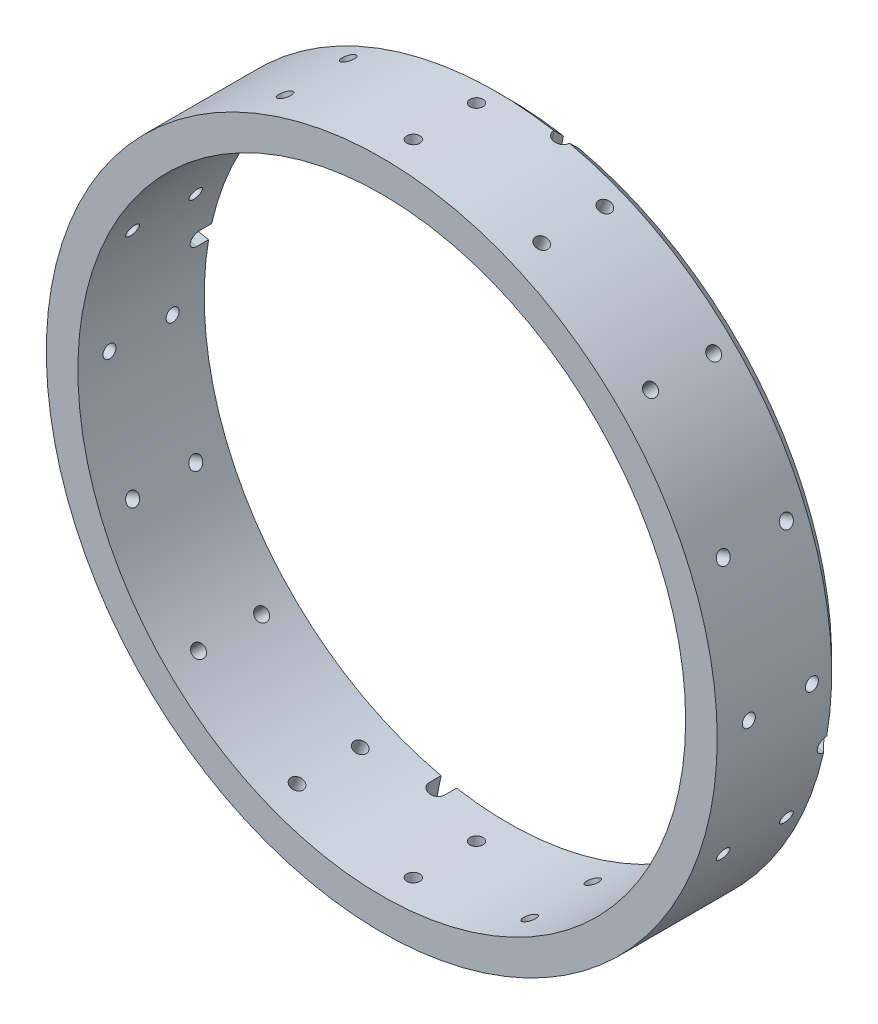
SolidWorks part; units mm, degrees
material "6063-T6"
ref_plane "Płaszczyzna przednia" through (0, 0, 0) normal (0, 0, 1) x (1, 0, 0)
ref_plane "Płaszczyzna górna" through (0, 0, 0) normal (0, 1, 0) x (1, 0, 0)
ref_plane "Płaszczyzna prawa" through (0, 0, 0) normal (1, 0, 0) x (0, 0, -1)
sketch "Szkic1" plane through (0, 0, 0) normal (0, 0, 1) x (1, 0, 0)
  circle A0 centre (0, 0) radius 85
  circle A1 centre (0, 0) radius 77
  dimension "D1" = 170
  dimension "D2" = 8
extrude "Dodanie-wyciągnięcie1" add sketch "Szkic1" along normal blind 32
sketch "Szkic2" plane through (0, 0, 32) normal (0, 0, 1) x (1, 0, 0)
  line L0 (0, 46.3429) -> (0, 98.4468) construction
  circle A0 centre (0, 0) radius 85 construction
  circle A1 centre (0, 0) radius 85
  point P6 (0, 85)
sketch3d "Szkic 3D1"
sketch "Szkic3" plane through (0, 85, 0) normal (0, 1, 0) x (1, 0, 0)
  line L0 (0, 18.1334) -> (0, -45.2976) construction
  line L1 (77, 0) -> (-77, 0) construction
  circle A0 centre (0, -8) radius 1.65
  circle A1 centre (0, -24) radius 1.65
  dimension "D1" = 3.3
  dimension "D2" = 3.3
  dimension "D3" = 8
  dimension "D4" = 16
extrude "Wytnij-wyciągnięcie1" cut sketch "Szkic3" against normal blind 32
pattern_circular "Szyk kołowy1" count 16 over 360 about axis through (0, 0, 32) along (0, 0, -1) of "Wytnij-wyciągnięcie1" reverse direction yes
chamfer "Sfazowanie1" distance 3 angle 45 1 edges at (85, 0, 0)
sketch "Szkic5" plane through (0, 0, 0) normal (0, 0, -1) x (-1, 0, 0)
  line L0 (0, 109.5264) -> (0, 0) construction
  line L1 (-23.4011, 117.6453) -> (0, 0) construction
  line L2 (-18.5397, 82.9535) -> (-16.9785, 75.1048)
  line L3 (-14.6165, 83.7338) -> (-13.0553, 75.8852)
  line L5 (-21.4395, 118.0355) -> (1.9616, 0.3902) construction
  line L6 (-25.3627, 117.2552) -> (-1.9616, -0.3902) construction
  circle A0 centre (0, 0) radius 85 construction
  circle A1 centre (0, 0) radius 77 construction
  arc A2 (-14.6165, 83.7338) -> (-18.5397, 82.9535) centre (0, 0) ccw
  arc A3 (-13.0553, 75.8852) -> (-16.9785, 75.1048) centre (0, 0) ccw
  dimension "D1" = 11.25
  dimension "D2" = 2
  dimension "D3" = 2
extrude "Wytnij-wyciągnięcie2" cut sketch "Szkic5" against normal blind 5
fillet "Zaokrąglenie2" radius 2 2 edges at (13.8359, 79.8095, 5) (17.7591, 79.0291, 5)
pattern_circular "Szyk kołowy4" count 4 over 360 about axis through (0, 0, 32) along (0, 0, -1) of "Zaokrąglenie2", "Wytnij-wyciągnięcie2" reverse direction yes
